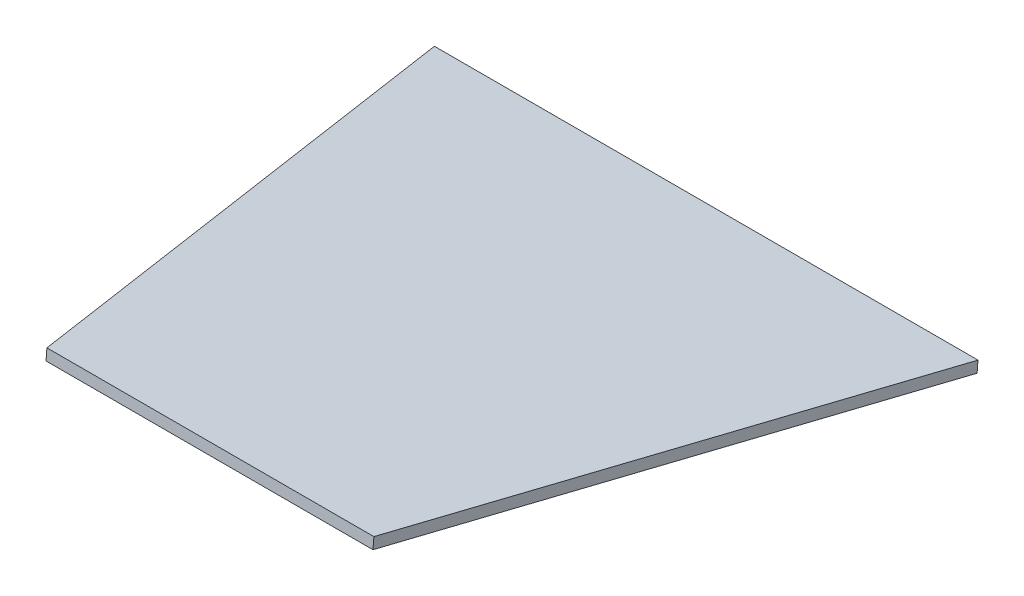
SolidWorks part; units mm, degrees
ref_plane "Front Plane" through (0, 0, 0) normal (0, 0, 1) x (1, 0, 0)
ref_plane "Top Plane" through (0, 0, 0) normal (0, 1, 0) x (1, 0, 0)
ref_plane "Right Plane" through (0, 0, 0) normal (1, 0, 0) x (0, 0, -1)
ref_plane "Plane1" through (-0.0001, -1585.0864, 130.7593) normal (0, -0.9966, 0.0822) x (-1, 0, 0)
sketch "Sketch1" plane through (-0.0001, -1585.0864, 130.7593) normal (0, -0.9966, 0.0822) x (-1, 0, 0)
  line L0 (927.9324, -1893.2884) -> (1306.8393, -1893.2884)
  line L1 (1306.8393, -1893.2884) -> (1432.3521, -1316.7398)
  line L2 (1432.3521, -1316.7398) -> (802.4196, -1316.7398)
  line L3 (802.4196, -1316.7398) -> (927.9324, -1893.2884)
  line L4 (802.4183, -1316.7398) -> (1432.3534, -1316.7398) construction
  line L5 (928.076, -1893.948) -> (801.0629, -1310.5075) construction
  line L6 (1433.7088, -1310.5075) -> (1306.6957, -1893.948) construction
  line L7 (1306.8419, -1893.2884) -> (927.9298, -1893.2884) construction
extrude "Boss-Extrude1" add sketch "Sketch1" along normal blind 12.7
